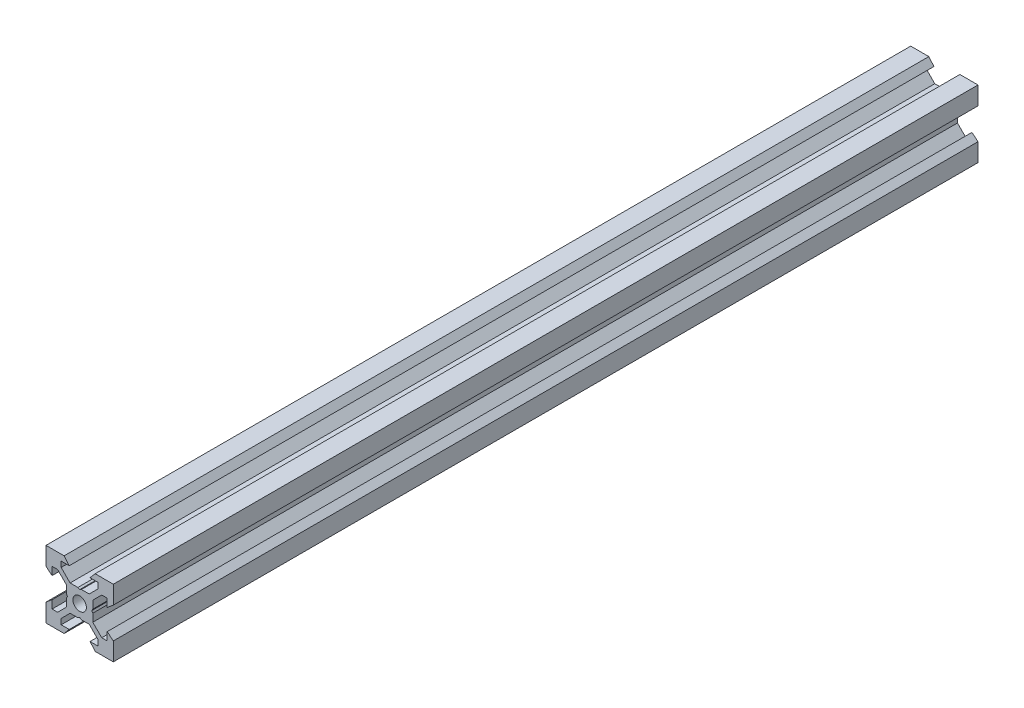
SolidWorks part; units mm, degrees
ref_plane "Front Plane" through (0, 0, 0) normal (0, 0, 1) x (1, 0, 0)
ref_plane "Top Plane" through (0, 0, 0) normal (0, 1, 0) x (1, 0, 0)
ref_plane "Right Plane" through (0, 0, 0) normal (1, 0, 0) x (0, 0, -1)
sketch "Sketch1" plane through (0, 0, 0) normal (0, 0, 1) x (1, 0, 0)
  line L0 (10, 10) -> (4.6104, 10) construction
  line L1 (10, 10) -> (10, 4.6104) construction
  line L2 (10, -10) -> (10, -4.6104) construction
  line L3 (10, -10) -> (4.6104, -10) construction
  line L4 (10, 10) -> (10, 4.6104)
  line L5 (6.5607, 5.5) -> (8.2, 5.5)
  line L6 (5.5, 8.2) -> (5.5, 6.5607)
  line L7 (10, 10) -> (4.6104, 10)
  line L8 (10, 10) -> (10, 4.6104)
  line L9 (6.5607, 5.5) -> (3.9, 2.8393)
  line L10 (5.5, 6.5607) -> (2.8393, 3.9)
  line L11 (10, 4.6104) -> (8.2, 3.1)
  line L12 (4.6104, 10) -> (3.1, 8.2)
  line L13 (8.2, 3.1) -> (8.2, 5.5)
  line L14 (3.1, 8.2) -> (5.5, 8.2)
  line L15 (-6.5607, 5.5) -> (-8.2, 5.5)
  line L16 (6.5607, -5.5) -> (8.2, -5.5)
  line L17 (3.1, -8.2) -> (5.5, -8.2)
  line L18 (8.2, -3.1) -> (8.2, -5.5)
  line L19 (4.6104, -10) -> (3.1, -8.2)
  line L20 (10, -4.6104) -> (8.2, -3.1)
  line L21 (0.5196, -3.9) -> (0, -3.6)
  line L22 (0.5196, 3.9) -> (0, 3.6)
  line L23 (3.6, 0) -> (3.9, -0.5196)
  line L24 (3.9, 0.5196) -> (3.6, 0)
  line L25 (3.9, 0.5196) -> (3.9, 2.8393)
  line L26 (2.8393, 3.9) -> (0.5196, 3.9)
  line L27 (3.9, -2.8393) -> (3.9, -0.5196)
  line L28 (2.8393, -3.9) -> (0.5196, -3.9)
  line L29 (5.5, -6.5607) -> (2.8393, -3.9)
  line L30 (6.5607, -5.5) -> (3.9, -2.8393)
  line L31 (10, -10) -> (10, -4.6104)
  line L32 (10, -10) -> (4.6104, -10)
  line L33 (5.5, -8.2) -> (5.5, -6.5607)
  line L34 (-6.5607, -5.5) -> (-8.2, -5.5)
  line L35 (10, -10) -> (10, -4.6104)
  line L36 (0, 0) -> (0, 8.2) construction
  line L37 (-10, -10) -> (-4.6104, -10) construction
  line L38 (-10, -10) -> (-10, -4.6104) construction
  line L39 (-10, 10) -> (-10, 4.6104) construction
  line L40 (-10, 10) -> (-4.6104, 10) construction
  line L41 (-10, -10) -> (-10, -4.6104)
  line L43 (-5.5, -8.2) -> (-5.5, -6.5607)
  line L44 (-10, -10) -> (-4.6104, -10)
  line L45 (-10, -10) -> (-10, -4.6104)
  line L46 (-6.5607, -5.5) -> (-3.9, -2.8393)
  line L47 (-5.5, -6.5607) -> (-2.8393, -3.9)
  line L48 (-2.8393, -3.9) -> (-0.5196, -3.9)
  line L49 (-3.9, -2.8393) -> (-3.9, -0.5196)
  line L50 (-2.8393, 3.9) -> (-0.5196, 3.9)
  line L51 (-3.9, 0.5196) -> (-3.9, 2.8393)
  line L52 (-3.9, 0.5196) -> (-3.6, 0)
  line L53 (-3.6, 0) -> (-3.9, -0.5196)
  line L54 (-0.5196, 3.9) -> (0, 3.6)
  line L55 (-0.5196, -3.9) -> (0, -3.6)
  line L56 (-10, -4.6104) -> (-8.2, -3.1)
  line L57 (-4.6104, -10) -> (-3.1, -8.2)
  line L58 (-8.2, -3.1) -> (-8.2, -5.5)
  line L59 (-3.1, -8.2) -> (-5.5, -8.2)
  line L60 (-10, -10) -> (10, -10) construction
  line L61 (-10, -10) -> (-10, 10) construction
  line L62 (-3.1, 8.2) -> (-5.5, 8.2)
  line L63 (-8.2, 3.1) -> (-8.2, 5.5)
  line L64 (-4.6104, 10) -> (-3.1, 8.2)
  line L65 (-10, 4.6104) -> (-8.2, 3.1)
  line L66 (-5.5, 6.5607) -> (-2.8393, 3.9)
  line L67 (-6.5607, 5.5) -> (-3.9, 2.8393)
  line L68 (-10, 10) -> (-10, 4.6104)
  line L69 (-10, 10) -> (-4.6104, 10)
  line L70 (-5.5, 8.2) -> (-5.5, 6.5607)
  line L71 (-10, 10) -> (10, 10) construction
  line L72 (-10, 10) -> (-10, 4.6104)
  line L73 (10, -10) -> (10, 10) construction
  line L74 (-10, -10) -> (10, 10) construction
  line L75 (-10, 10) -> (10, -10) construction
  circle A0 centre (0, 0) radius 2
  dimension "D7" = 4
  dimension "D1" = 20
  dimension "D2" = 5.3896
  dimension "D3" = 4.5
  dimension "D4" = 50
  dimension "D5" = 1.8
  dimension "D6" = 1.5104
  dimension "D8" = 5.5
  dimension "D9" = 120
  dimension "D10" = 0.3
  dimension "D11" = 2.3197
  dimension "D12" = 7.8
  dimension "D13" = 7.8
  dimension "D14" = 1.5
  dimension "D15" = 2.6607
extrude "Boss-Extrude1" add sketch "Sketch1" along normal mid plane 257 contours L70 L62 L64 L69 L68 L65 L63 L15 L67 L51 L52 L53 L49 L46 L34 L58 L56 L41 L44 L57 L59 L43 L47 L48 L55 L21 L28 L29 L33 L17 L19 L32 L31 L20 L18 L16 L30 L27 L23 L24 L25 L9 L5 L13 L11 L4 L7 L12 L14 L6 L10 region at (9.7172, 7.3052, 0)
